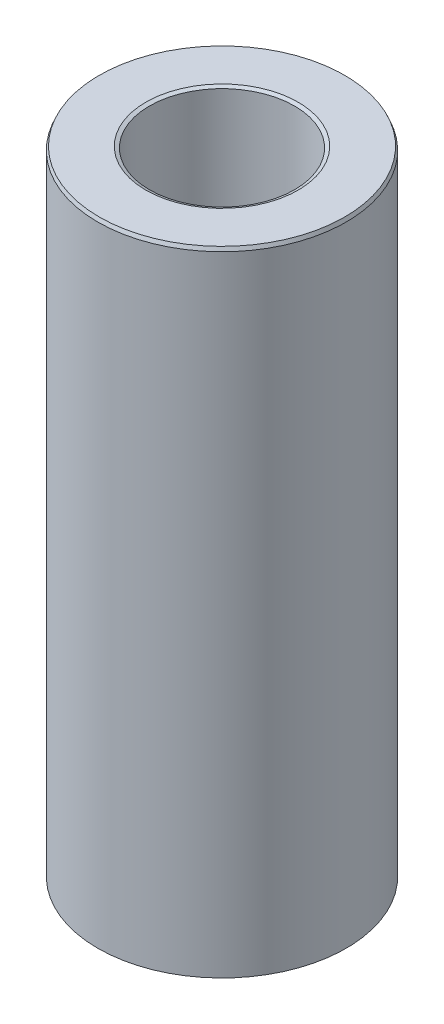
SolidWorks part; units mm, degrees
ref_plane "Front Plane" through (0, 0, 0) normal (0, 0, 1) x (1, 0, 0)
ref_plane "Top Plane" through (0, 0, 0) normal (0, 1, 0) x (1, 0, 0)
ref_plane "Right Plane" through (0, 0, 0) normal (1, 0, 0) x (0, 0, -1)
sketch "Sketch1" plane through (0, 0, 0) normal (0, 1, 0) x (1, 0, 0)
  circle A0 centre (0, 0) radius 50
  dimension "SLEEVE_OD" = 100
extrude "Boss-Extrude1" add sketch "Sketch1" along normal blind 255.2046
sketch "Sketch2" plane through (0, 0, 0) normal (0, 1, 0) x (1, 0, 0)
  circle A0 centre (0, 0) radius 29.2106
  dimension "BORE_D" = 58.4212
extrude "Cut-Extrude1" cut sketch "Sketch2" along normal through all
chamfer "Chamfer1" distance 1.4593 angle 22.304 4 edges at (0, 255.2046, 29.2106) (0, 0, 29.2106) (0, 0, 50) (0, 255.2046, 50) first distance on face at (0, 255.2046, 29.2106) first distance on face at (0, 0, 29.2106) first distance on face at (0, 255.2046, 50)
